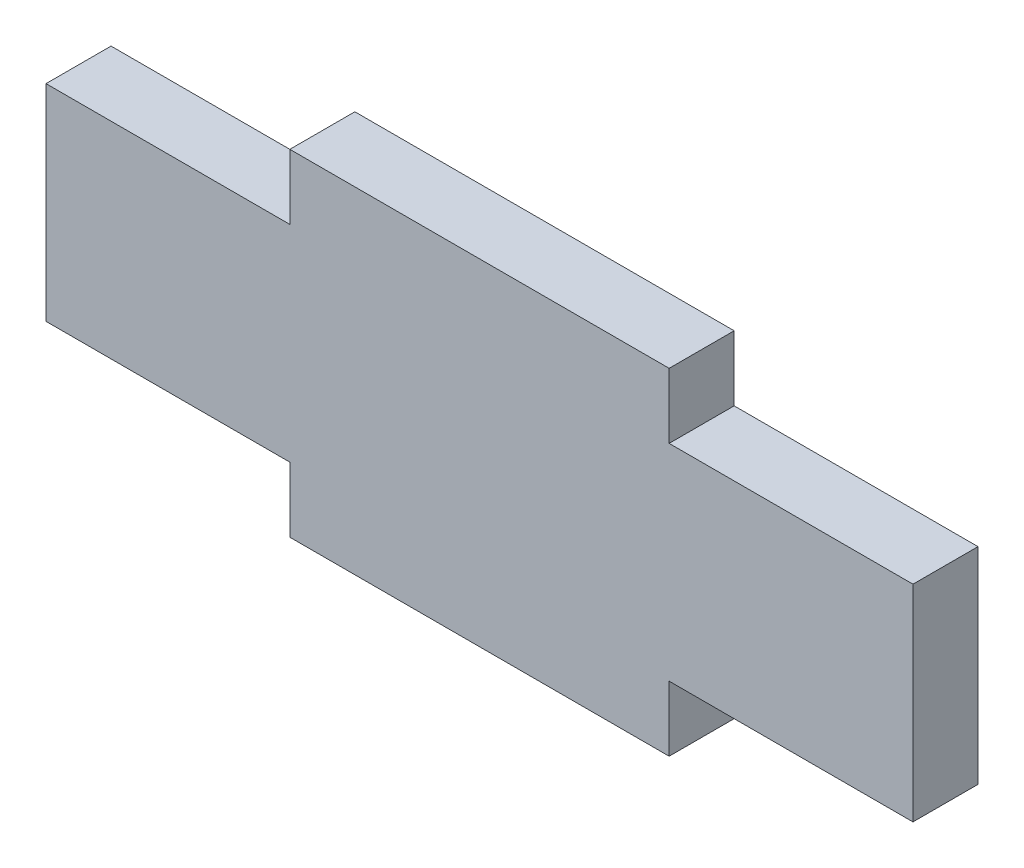
SolidWorks part; units mm, degrees
ref_plane "Plano frontal" through (0, 0, 0) normal (0, 0, 1) x (1, 0, 0)
ref_plane "Plano superior" through (0, 0, 0) normal (0, 1, 0) x (1, 0, 0)
ref_plane "Plano direito" through (0, 0, 0) normal (1, 0, 0) x (0, 0, -1)
sketch "Esboço1" plane through (0, 0, 0) normal (0, 0, 1) x (1, 0, 0)
  line L0 (0, 0) -> (40, 0) construction
  line L1 (-40, -9.5) -> (40, -9.5)
  line L2 (-40, -9.5) -> (-40, 9.5)
  line L3 (-40, 9.5) -> (40, 9.5)
  line L4 (40, -9.5) -> (40, 9.5)
  line L5 (-40, -9.5) -> (40, 9.5) construction
  line L6 (-40, 9.5) -> (40, -9.5) construction
  line L7 (17.5, 15.5) -> (-17.5, 15.5)
  line L8 (17.5, 15.5) -> (17.5, 9.5)
  line L9 (17.5, 9.5) -> (-17.5, 9.5)
  line L10 (-17.5, 15.5) -> (-17.5, 9.5)
  line L11 (17.5, 15.5) -> (-17.5, 9.5) construction
  line L12 (17.5, 9.5) -> (-17.5, 15.5) construction
  line L13 (17.5, -9.5) -> (-17.5, -9.5)
  line L14 (-17.5, -15.5) -> (-17.5, -9.5)
  line L15 (17.5, -15.5) -> (-17.5, -15.5)
  line L16 (17.5, -15.5) -> (17.5, -9.5)
  point P0 (0, 0)
  point P6 (0, 12.5)
  dimension "D1" = 6
  dimension "D2" = 35
  dimension "D3" = 19
  dimension "D4" = 80
extrude "Ressalto-extrusão1" add sketch "Esboço1" along normal blind 6 contours L1 L4 L3 L2 | L7 L10 L3 L8 | L15 L16 L1 L14 region at (0, 0, 0) region at (0, -12.5, 0) region at (0, 12.5, 0)
